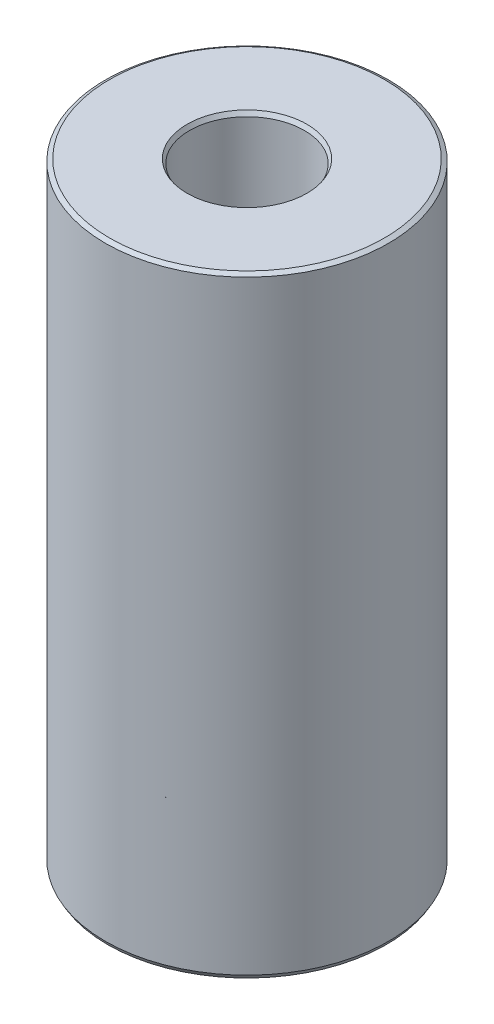
SolidWorks part; units mm, degrees
ref_plane "Front Plane" through (0, 0, 0) normal (0, 0, 1) x (1, 0, 0)
ref_plane "Top Plane" through (0, 0, 0) normal (0, 1, 0) x (1, 0, 0)
ref_plane "Right Plane" through (0, 0, 0) normal (1, 0, 0) x (0, 0, -1)
sketch "Sketch1" plane through (0, 0, 0) normal (0, 1, 0) x (1, 0, 0)
  circle A0 centre (0, 0) radius 50
  dimension "SLEEVE_OD" = 100
extrude "Boss-Extrude1" add sketch "Sketch1" along normal blind 215.8179
sketch "Sketch2" plane through (0, 0, 0) normal (0, 1, 0) x (1, 0, 0)
  circle A0 centre (0, 0) radius 20.2946
  dimension "BORE_D" = 40.5892
extrude "Cut-Extrude1" cut sketch "Sketch2" along normal through all
chamfer "Chamfer1" distance 0.8572 angle 60 4 edges at (0, 215.8179, 20.2946) (0, 0, 20.2946) (0, 0, 50) (0, 215.8179, 50) first distance on face at (0, 215.8179, 20.2946) first distance on face at (0, 0, 20.2946) first distance on face at (0, 215.8179, 50)
